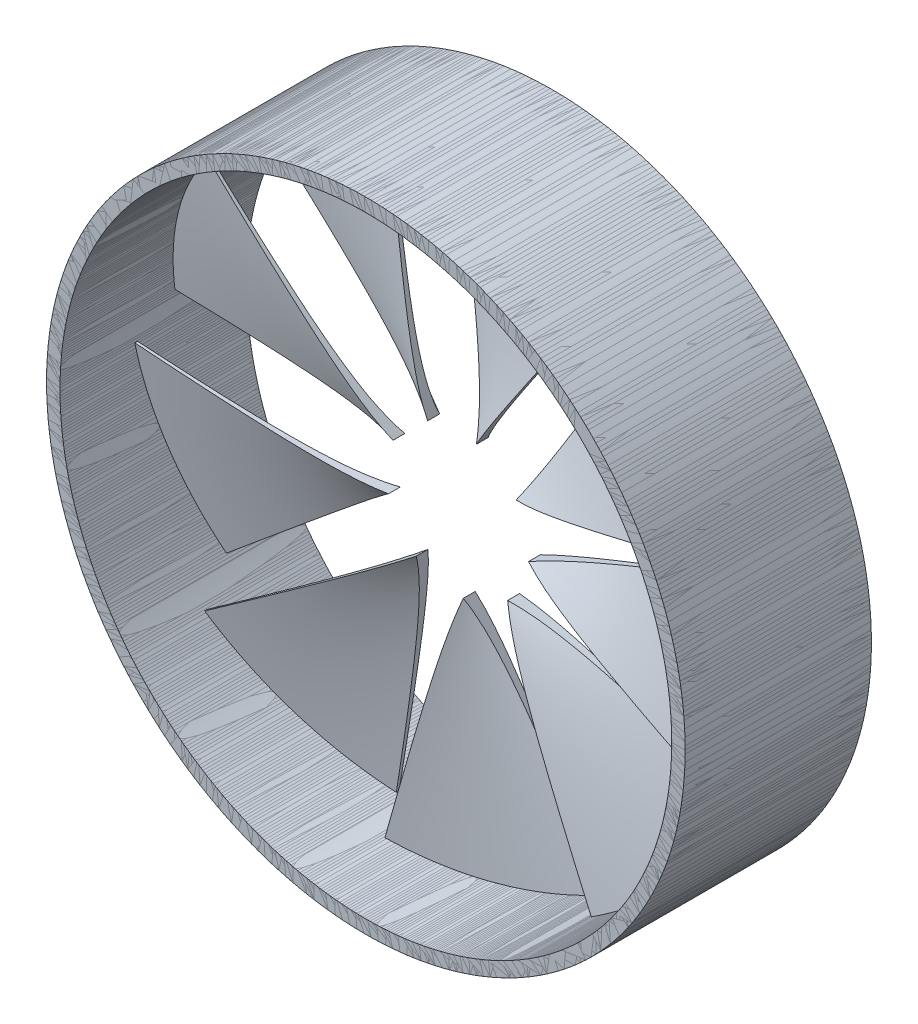
SolidWorks part; units mm, degrees
ref_plane "Front Plane" through (0, 0, 0) normal (0, 0, 1) x (1, 0, 0)
ref_plane "Top Plane" through (0, 0, 0) normal (0, 1, 0) x (1, 0, 0)
ref_plane "Right Plane" through (0, 0, 0) normal (1, 0, 0) x (0, 0, -1)
sketch "Sketch1" plane through (0, 0, 0) normal (0, 0, 1) x (1, 0, 0)
  circle A0 centre (0, 0) radius 119.994
  dimension "D1" = 239.988
curve "Helix/Spiral1" pitch 150 height 30 radius 119.994 left hand yes centre (0, 0, 0) axis (0, 0, 1) start towards (-1, 0, 0)
sketch "Sketch2" plane through (0, 0, 0) normal (0, 0, 1) x (1, 0, 0)
  line L1 (-119.994, 0) -> (-25.2, 0)
  line L2 (-119.994, 0) -> (-119.994, 5)
  line L3 (-119.994, 5) -> (-25.2, 5)
  line L4 (-25.2, 0) -> (-25.2, 5)
  spline S0 degree 3 poles (-119.994, 0) (-119.994, 5.5804) (-119.213, 16.7563) (-115.721, 33.1819) (-109.9767, 48.9649) (-102.0919, 63.794) (-92.2199, 77.3817) (-80.5531, 89.4631) (-67.3177, 99.8035) (-52.775, 108.2003) (-42.3875, 112.3966) (-37.0802, 114.1211) knots 0 0 0 0 0.111111 0.222222 0.333333 0.444444 0.555556 0.666667 0.777778 0.888889 1 1 1 1 construction
  dimension "D3" = 25.2
sweep "Sweep1" add profiles "Sketch2" path "Helix/Spiral1"
ref_plane "Plane1" through (0, 0, 0) normal (0, 0, 1) x (1, 0, 0)
sketch "Sketch9" plane through (0, 0, 0) normal (0, 0, 1) x (1, 0, 0)
  line L0 (-24.2292, 11.4837) -> (-90.9717, 78.2263)
  line L1 (-24.2292, 11.4837) -> (-119.4292, 11.4837)
  arc A0 (-90.9717, 78.2263) -> (-119.4292, 11.4837) centre (0, 0) ccw
  dimension "D2" = 45
  dimension "D1" = 119.98
  dimension "D3" = 95.2
extrude "Cut-Extrude1" cut sketch "Sketch9" along normal blind 40 flip side to cut
sketch "Sketch10" plane through (0, 0, 0) normal (0, 0, 1) x (1, 0, 0)
  circle A0 centre (0, 0) radius 114.994
  circle A1 centre (0, 0) radius 119.994
  dimension "D2" = 229.988
extrude "Boss-Extrude1" add sketch "Sketch10" along normal blind 45 and the other way blind 25
pattern_circular "CirPattern2" count 9 over 360 about axis through (0, 0, -25) along (0, 0, 1) reverse direction yes of bodies 103
equation "\"ThrusterDim\"= 140mm"
equation "\"hatchHoleDiameter\"= 600mm"
equation "\"hullThickness\"= 120mm"
equation "\"gasketHullInterconnectWidth\"= 100mm"
equation "\"collarThickness\"= 15"
equation "\"hatchTunnelLength\"=200"
equation "\"oRingDiameter\"=2"
equation "\"boltPatternRadiusInterconnect\"=500"
equation "\"interconnectBoltDiameter\"=30"
equation "\"hatchShaftDiameter\"=20"
equation "\"hatchMinima\"=50"
equation "\"hullDiameter\"=2000"
equation "\"hatchMaxima\"=180"
equation "\"bushingFlatHatch\"=15"
equation "\"hingePivotDiameter\"=20"
equation "\"handleWidth\"=250"
equation "\"handleHeight\"=160"
equation "\"handleThickness\"=25"
equation "\"FrameLength\"= 4300"
equation "\"FrameMidLength\"= 3000"
equation "\"TubeOD\"= 100"
equation "\"FrameBackFlat\"= 800"
equation "\"TubeWall\"=15"
equation "\"TopMemberAngle\"=120"
equation "\"FrameHight\"= 2500"
equation "\"D1@Sketch1\"=\"ThrusterDim\" *2 *0.8571"
equation "\"D2@Sketch10\"=\"ThrusterDim\" *2 *0.8571-10"
equation "\"th\"=16.5237"
equation "\"D3@Sketch2\"=\"ThrusterDim\" *0.18"
equation "\"D1@Sketch9\"=\"ThrusterDim\" *0.857"
equation "\"D3@Sketch9\"=\"ThrusterDim\" *0.68"
